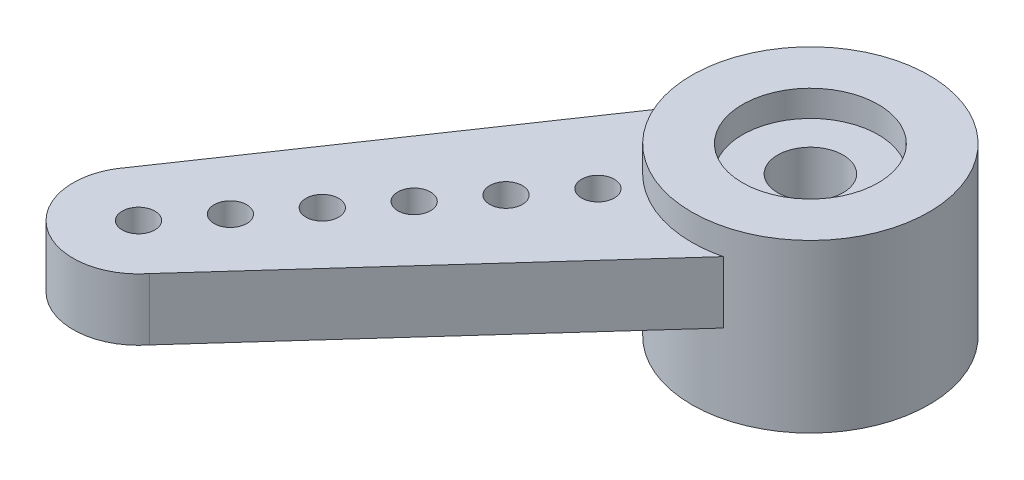
SolidWorks part; units mm, degrees
ref_plane "Front Plane" through (0, 0, 0) normal (0, 0, 1) x (1, 0, 0)
ref_plane "Top Plane" through (0, 0, 0) normal (0, 1, 0) x (1, 0, 0)
ref_plane "Right Plane" through (0, 0, 0) normal (1, 0, 0) x (0, 0, -1)
sketch "Sketch1" plane through (0, 0, 0) normal (0, 1, 0) x (1, 0, 0)
  circle A0 centre (0, 0) radius 3.625
  circle A1 centre (0, 0) radius 2.075
extrude "Boss-Extrude1" add sketch "Sketch1" along normal blind 2.41
sketch "Sketch2" plane through (0, 2.41, 0) normal (0, 1, 0) x (1, 0, 0)
  line L4 (-10.6055, -10.2672) -> (-3.625, 0)
  line L5 (-7.4595, -12.7376) -> (0.8596, -3.5216)
  circle A0 centre (0, 0) radius 1
  arc A1 (0.8596, -3.5216) -> (-3.625, 0) centre (0, 0) ccw
  arc A2 (-10.6055, -10.2672) -> (-7.4595, -12.7376) centre (-9.0325, -11.5024) ccw
  circle A4 centre (-9.0325, -11.5024) radius 0.5
  circle A5 centre (-7.7973, -9.9294) radius 0.5
  circle A6 centre (-6.5621, -8.3564) radius 0.5
  circle A7 centre (-5.3268, -6.7835) radius 0.5
  circle A8 centre (-4.0916, -5.2105) radius 0.5
  circle A9 centre (-2.8564, -3.6375) radius 0.5
  point P7 (-2.2388, -2.851)
extrude "Boss-Extrude3" add sketch "Sketch2" along normal blind 1.89
extrude "Boss-Extrude4" add sketch "Sketch1<2>" along normal blind 0.8 from surface starting at face at (-4.0916, 4.3, 5.7105)
sketch "Sketch1<2>" plane through (0, 0, 0) normal (0, 1, 0) x (1, 0, 0) same geometry as "Sketch1"
